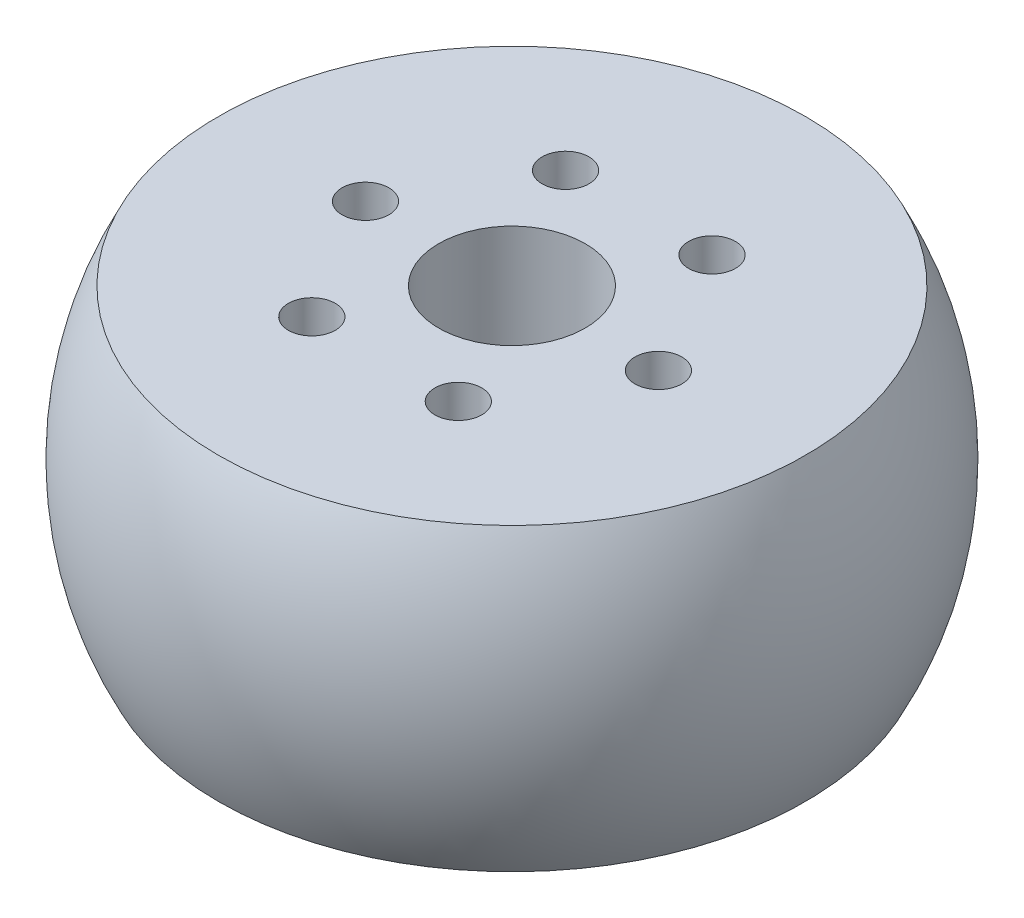
SolidWorks part; units mm, degrees
ref_plane "Front Plane" through (0, 0, 0) normal (0, 0, 1) x (1, 0, 0)
ref_plane "Top Plane" through (0, 0, 0) normal (0, 1, 0) x (1, 0, 0)
ref_plane "Right Plane" through (0, 0, 0) normal (1, 0, 0) x (0, 0, -1)
sketch "Sketch1" plane through (0, 0, 0) normal (1, 0, 0) x (0, 0, -1)
  line L0 (0, -6.5) -> (0, 6.5) construction
  line L1 (3.175, 6.5) -> (12.7233, 6.5)
  line L2 (3.175, 6.5) -> (3.175, -6.5)
  line L3 (3.175, -6.5) -> (12.7233, -6.5)
  line L4 (14.2875, 0) -> (0, 0) construction
  circle A0 centre (0, 0) radius 14.2875 construction
  arc A1 (12.7233, 6.5) -> (12.7233, -6.5) centre (0, 0) cw
  point P4 (0, 0)
  dimension "D1" = 6.35
  dimension "D2" = 13
  dimension "D3" = 14.2875
revolve "Revolve1" add sketch "Sketch1" angle 360 about L0
sketch "Sketch3" plane through (0, 0, 0) normal (0, 1, 0) x (1, 0, 0)
  line L0 (0, 0) -> (6.35, 0) construction
  circle A0 centre (6.35, 0) radius 1.016
  dimension "D1" = 2.032
  dimension "D2" = 6.35
extrude "Cut-Extrude1" cut sketch "Sketch3" against normal through all both and the other way through all
pattern_circular "CirPattern1" count 6 over 360 about axis through (0, -6.5, 0) along (0, -1, 0) of "Cut-Extrude1" reverse direction yes
